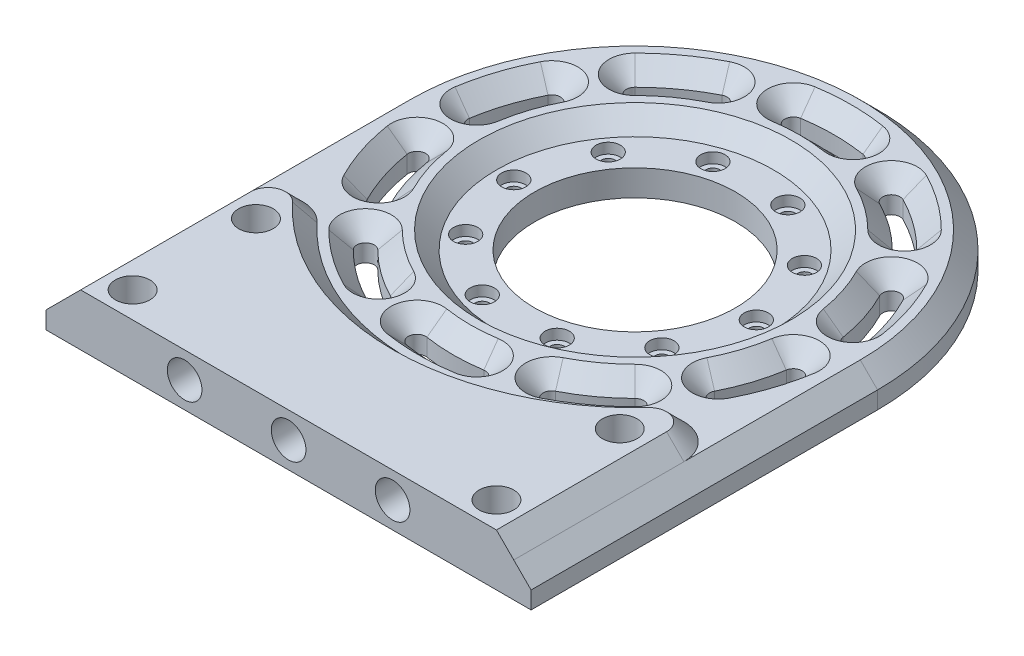
SolidWorks part; units mm, degrees
ref_plane "Front Plane" through (0, 0, 0) normal (0, 0, 1) x (1, 0, 0)
ref_plane "Top Plane" through (0, 0, 0) normal (0, 1, 0) x (1, 0, 0)
ref_plane "Right Plane" through (0, 0, 0) normal (1, 0, 0) x (0, 0, -1)
sketch "Sketch1" plane through (0, 0, 0) normal (0, 1, 0) x (1, 0, 0)
  line L0 (-70, 0) -> (-70, -100)
  line L1 (70, 0) -> (70, -100)
  line L2 (0, -100) -> (70, -100)
  line L3 (0, -100) -> (-70, -100)
  circle A2 centre (0, 0) radius 70
  circle A3 centre (0, 0) radius 29
  circle A4 centre (0, 0) radius 40
  circle A5 centre (-35, 0) radius 2
  circle A6 centre (-28.3156, 20.5725) radius 2
  circle A7 centre (-10.8156, 33.287) radius 2
  circle A8 centre (10.8156, 33.287) radius 2
  circle A9 centre (28.3156, 20.5725) radius 2
  circle A10 centre (35, 0) radius 2
  circle A11 centre (28.3156, -20.5725) radius 2
  circle A12 centre (10.8156, -33.287) radius 2
  circle A13 centre (-10.8156, -33.287) radius 2
  circle A14 centre (-28.3156, -20.5725) radius 2
  circle A15 centre (0, 0) radius 35
  point P36 (0, 0)
  dimension "D1" = 10
extrude "Boss-Extrude2" add sketch "Sketch1" along normal blind 10 contours A12 A15 A11 A10 A9 A8 A7 A6 A5 A14 A13 A3 | A4 A15 A12 A13 A14 A5 A6 A7 A8 A9 A10 A11 | A2 A4 | A2 L0 L3 L2 L1 region at (0, 0, 74.778) region at (0, 0, -68.0201) region at (-38.8686, 0, 0) region at (-32.8564, 0, -2.0832)
sketch "Sketch4" plane through (0, 10, 0) normal (0, 1, 0) x (1, 0, 0)
  circle A0 centre (0, 0) radius 29
  circle A1 centre (0, 0) radius 40
extrude "Cut-Extrude5" cut sketch "Sketch4" against normal blind 5
chamfer "Chamfer11" distance 5 angle 45 4 edges at (70, 10, 50) (0, 10, -70) (-70, 10, 50) (0, 10, 40)
sketch "Sketch7" plane through (0, 10, 0) normal (0, 1, 0) x (1, 0, 0)
  line L0 (0, 0) -> (-55, 0)
  line L1 (0, 0) -> (-28.3156, 20.5725)
  line L2 (-28.3156, 20.5725) -> (-44.4959, 32.3282)
  line L3 (0, 0) -> (-54.3229, 8.6039)
  line L4 (0, 0) -> (-52.3081, 16.9959)
  line L5 (0, 0) -> (-49.0054, 24.9695)
  circle A0 centre (0, 0) radius 55
  arc A1 (-49.0054, 24.9695) -> (-54.3229, 8.6039) centre (0, 0) ccw construction
  arc A2 (-51.2329, 26.1045) -> (-56.7921, 8.995) centre (0, 0) ccw
  arc A3 (-46.7778, 23.8345) -> (-51.8536, 8.2128) centre (0, 0) ccw
  arc A4 (-46.7778, 23.8345) -> (-51.2329, 26.1045) centre (-49.0054, 24.9695) ccw
  arc A5 (-56.7921, 8.995) -> (-51.8536, 8.2128) centre (-54.3229, 8.6039) ccw
  arc A6 (-24.9695, 49.0054) -> (-38.8909, 38.8909) centre (0, 0) ccw construction
  arc A7 (-26.1045, 51.2329) -> (-40.6586, 40.6586) centre (0, 0) ccw
  arc A8 (-23.8345, 46.7778) -> (-37.1231, 37.1231) centre (0, 0) ccw
  arc A9 (-23.8345, 46.7778) -> (-26.1045, 51.2329) centre (-24.9695, 49.0054) ccw
  arc A10 (-40.6586, 40.6586) -> (-37.1231, 37.1231) centre (-38.8909, 38.8909) ccw
  arc A11 (8.6039, 54.3229) -> (-8.6039, 54.3229) centre (0, 0) ccw construction
  arc A12 (8.995, 56.7921) -> (-8.995, 56.7921) centre (0, 0) ccw
  arc A13 (8.2128, 51.8536) -> (-8.2128, 51.8536) centre (0, 0) ccw
  arc A14 (8.2128, 51.8536) -> (8.995, 56.7921) centre (8.6039, 54.3229) ccw
  arc A15 (-8.995, 56.7921) -> (-8.2128, 51.8536) centre (-8.6039, 54.3229) ccw
  arc A16 (38.8909, 38.8909) -> (24.9695, 49.0054) centre (0, 0) ccw construction
  arc A17 (40.6586, 40.6586) -> (26.1045, 51.2329) centre (0, 0) ccw
  arc A18 (37.1231, 37.1231) -> (23.8345, 46.7778) centre (0, 0) ccw
  arc A19 (37.1231, 37.1231) -> (40.6586, 40.6586) centre (38.8909, 38.8909) ccw
  arc A20 (26.1045, 51.2329) -> (23.8345, 46.7778) centre (24.9695, 49.0054) ccw
  arc A21 (54.3229, 8.6039) -> (49.0054, 24.9695) centre (0, 0) ccw construction
  arc A22 (56.7921, 8.995) -> (51.2329, 26.1045) centre (0, 0) ccw
  arc A23 (51.8536, 8.2128) -> (46.7778, 23.8345) centre (0, 0) ccw
  arc A24 (51.8536, 8.2128) -> (56.7921, 8.995) centre (54.3229, 8.6039) ccw
  arc A25 (51.2329, 26.1045) -> (46.7778, 23.8345) centre (49.0054, 24.9695) ccw
  arc A26 (49.0054, -24.9695) -> (54.3229, -8.6039) centre (0, 0) ccw construction
  arc A27 (51.2329, -26.1045) -> (56.7921, -8.995) centre (0, 0) ccw
  arc A28 (46.7778, -23.8345) -> (51.8536, -8.2128) centre (0, 0) ccw
  arc A29 (46.7778, -23.8345) -> (51.2329, -26.1045) centre (49.0054, -24.9695) ccw
  arc A30 (56.7921, -8.995) -> (51.8536, -8.2128) centre (54.3229, -8.6039) ccw
  arc A31 (24.9695, -49.0054) -> (38.8909, -38.8909) centre (0, 0) ccw construction
  arc A32 (26.1045, -51.2329) -> (40.6586, -40.6586) centre (0, 0) ccw
  arc A33 (23.8345, -46.7778) -> (37.1231, -37.1231) centre (0, 0) ccw
  arc A34 (23.8345, -46.7778) -> (26.1045, -51.2329) centre (24.9695, -49.0054) ccw
  arc A35 (40.6586, -40.6586) -> (37.1231, -37.1231) centre (38.8909, -38.8909) ccw
  arc A36 (-8.6039, -54.3229) -> (8.6039, -54.3229) centre (0, 0) ccw construction
  arc A37 (-8.995, -56.7921) -> (8.995, -56.7921) centre (0, 0) ccw
  arc A38 (-8.2128, -51.8536) -> (8.2128, -51.8536) centre (0, 0) ccw
  arc A39 (-8.2128, -51.8536) -> (-8.995, -56.7921) centre (-8.6039, -54.3229) ccw
  arc A40 (8.995, -56.7921) -> (8.2128, -51.8536) centre (8.6039, -54.3229) ccw
  arc A41 (-38.8909, -38.8909) -> (-24.9695, -49.0054) centre (0, 0) ccw construction
  arc A42 (-40.6586, -40.6586) -> (-26.1045, -51.2329) centre (0, 0) ccw
  arc A43 (-37.1231, -37.1231) -> (-23.8345, -46.7778) centre (0, 0) ccw
  arc A44 (-37.1231, -37.1231) -> (-40.6586, -40.6586) centre (-38.8909, -38.8909) ccw
  arc A45 (-26.1045, -51.2329) -> (-23.8345, -46.7778) centre (-24.9695, -49.0054) ccw
  arc A46 (-54.3229, -8.6039) -> (-49.0054, -24.9695) centre (0, 0) ccw construction
  arc A47 (-56.7921, -8.995) -> (-51.2329, -26.1045) centre (0, 0) ccw
  arc A48 (-51.8536, -8.2128) -> (-46.7778, -23.8345) centre (0, 0) ccw
  arc A49 (-51.8536, -8.2128) -> (-56.7921, -8.995) centre (-54.3229, -8.6039) ccw
  arc A50 (-51.2329, -26.1045) -> (-46.7778, -23.8345) centre (-49.0054, -24.9695) ccw
  point P11 (-52.3081, 16.9959)
  point P20 (-32.3282, 44.4959)
  point P27 (0, 55)
  point P34 (32.3282, 44.4959)
  point P41 (52.3081, 16.9959)
  point P48 (52.3081, -16.9959)
  point P55 (32.3282, -44.4959)
  point P62 (0, -55)
  point P69 (-32.3282, -44.4959)
  point P76 (-52.3081, -16.9959)
  point P81 (0, 0)
  dimension "D1" = 9
  dimension "D4" = 10
  dimension "D2" = 9
  dimension "D3" = 9
extrude "Cut-Extrude8" cut sketch "Sketch7" against normal blind 10 contours A8 A10 A7 A9 | A13 A15 A12 A14 | A18 A20 A17 A19 | A22 A25 A23 A24 | A27 A30 A28 A29 | A32 A35 A33 A34 | A37 A40 A38 A39 | A42 A45 A43 A44 | A47 A50 A48 A49 | A2 A5 A3 A4
chamfer "Chamfer16" distance 5 angle 45 40 edges at (-54.6857, 10, 17.7685) (-54.7139, 10, 6.1347) (-47.8704, 10, 27.197) (-49.9305, 10, 16.2234) (-33.7977, 10, 46.5185) (-40.6586, 10, 37.1231) (-22.742, 10, 50.1403) (-30.8587, 10, 42.4734) (0, 10, 57.5) (-11.0731, 10, 53.9318) (11.0731, 10, 53.9318) (0, 10, 52.5) (33.7977, 10, 46.5185) (22.742, 10, 50.1403) (40.6586, 10, 37.1231) (30.8587, 10, 42.4734) (49.9305, 10, 16.2234) (47.8704, 10, 27.197) (54.7139, 10, 6.1347) (54.6857, 10, 17.7685) (49.9305, 10, -16.2234) (54.7139, 10, -6.1347) (47.8704, 10, -27.197) (54.6857, 10, -17.7685) (30.8587, 10, -42.4734) (40.6586, 10, -37.1231) (22.742, 10, -50.1403) (33.7977, 10, -46.5185) (0, 10, -52.5) (11.0731, 10, -53.9318) (-11.0731, 10, -53.9318) (0, 10, -57.5) (-30.8587, 10, -42.4734) (-22.742, 10, -50.1403) (-40.6586, 10, -37.1231) (-33.7977, 10, -46.5185) (-49.9305, 10, -16.2234) (-47.8704, 10, -27.197) (-54.7139, 10, -6.1347) (-54.6857, 10, -17.7685)
sketch "Sketch8" plane through (0, 10, 0) normal (0, 1, 0) x (1, 0, 0)
  line L2 (65, -100) -> (-65, -100) construction
  line L12 (-60, -50.8932) -> (-60, -100)
  line L13 (60, -100) -> (60, -50.8932)
  line L17 (-60, -100) -> (60, -100)
  arc A2 (-51.3333, -47.4939) -> (51.3333, -47.4939) centre (0, 0.0969) ccw
  arc A3 (60, -50.8932) -> (51.3333, -47.4939) centre (55, -50.8932) ccw
  arc A4 (-51.3333, -47.4939) -> (-60, -50.8932) centre (-55, -50.8932) ccw
  dimension "D1" = 5
extrude "Boss-Extrude3" add sketch "Sketch8" along normal blind 5
sketch "Sketch9" plane through (0, 15, 0) normal (0, 1, 0) x (1, 0, 0)
  line L9 (52.5, -56.9118) -> (52.5, -92.5)
  line L10 (52.5, -92.5) -> (-52.5, -92.5)
  line L11 (-52.5, -92.5) -> (-52.5, -56.9118)
  line L12 (52.5, -56.9118) -> (52.5, -92.5)
  line L13 (52.5, -92.5) -> (-52.5, -92.5)
  line L14 (-52.5, -92.5) -> (-52.5, -56.9118)
  circle A9 centre (-52.5, -56.9118) radius 5
  circle A10 centre (52.5, -56.9118) radius 5
  arc A11 (-52.5, -56.9118) -> (52.5, -56.9118) centre (0, 0.0969) ccw
  arc A12 (-52.5, -56.9118) -> (52.5, -56.9118) centre (0, 0.0969) ccw
  circle A13 centre (52.5, -92.5) radius 5
  circle A14 centre (-52.5, -92.5) radius 5
  dimension "D1" = 7.5
extrude "Cut-Extrude9" cut sketch "Sketch9" against normal blind 10 contours L14 A12 A9 | A12 L14 A9 | L14 A14 L13 | L13 A14 L14 | L13 A13 L12 | L12 A13 L13 | A12 A10 L12 | A10 A12 L12 region at (52.7089, 15, 56.4508) region at (51.1613, 15, 59.8666) region at (53.2074, 15, 93.2074) region at (50.3779, 15, 90.3779) region at (-52.7089, 15, 56.4508) region at (-51.1613, 15, 59.8666) region at (-53.2074, 15, 93.2074) region at (-50.3779, 15, 90.3779)
chamfer "Chamfer18" distance 5 angle 45 5 edges at (60, 10, 75.4466) (56.8257, 10, 46.2385) (0, 10, 69.9031) (-56.8257, 10, 46.2385) (-60, 10, 75.4466)
sketch "Sketch12" plane through (0, 5, 0) normal (0, 1, 0) x (1, 0, 0)
  circle A0 centre (-35, 0) radius 3.5
  circle A1 centre (-28.3156, 20.5725) radius 3.5
  circle A2 centre (-10.8156, 33.287) radius 3.5
  circle A3 centre (10.8156, 33.287) radius 3.5
  circle A4 centre (28.3156, 20.5725) radius 3.5
  circle A5 centre (35, 0) radius 3.5
  circle A6 centre (28.3156, -20.5725) radius 3.5
  circle A7 centre (10.8156, -33.287) radius 3.5
  circle A8 centre (-10.8156, -33.287) radius 3.5
  circle A9 centre (-28.3156, -20.5725) radius 3.5
  point P23 (0, 0)
  dimension "D1" = 10
extrude "Cut-Extrude12" cut sketch "Sketch12" against normal blind 3
sketch "Sketch13" plane through (0, 0, 0) normal (0, -1, 0) x (1, 0, 0)
  circle A0 centre (0, 0) radius 29
  circle A1 centre (0, 0) radius 40
  circle A2 centre (0, 0) radius 45
  circle A3 centre (-35, 0) radius 2
  circle A4 centre (-28.3156, 20.5725) radius 2
  circle A5 centre (-10.8156, 33.287) radius 2
  circle A6 centre (10.8156, 33.287) radius 2
  circle A7 centre (28.3156, 20.5725) radius 2
  circle A8 centre (35, 0) radius 2
  circle A9 centre (28.3156, -20.5725) radius 2
  circle A10 centre (10.8156, -33.287) radius 2
  circle A11 centre (-10.8156, -33.287) radius 2
  circle A12 centre (-28.3156, -20.5725) radius 2
  point P28 (0, 0)
  dimension "D1" = 10
extrude "Boss-Extrude4" add sketch "Sketch13" along normal blind 2.5 contours A1 A0 | A2 A1 region at (-38.8686, 0, 0) region at (-43.7272, 0, 0)
sketch "Sketch14" plane through (0, 0, 100) normal (0, 0, 1) x (1, 0, 0)
  line L0 (-60, 15) -> (-60, 0)
  line L1 (60.0315, 15) -> (60.0315, 0)
  line L2 (-60, 7.5) -> (-44.9961, 7.5)
  line L3 (-44.9961, 7.5) -> (-29.9921, 7.5)
  line L4 (-29.9921, 7.5) -> (0.0158, 7.5)
  line L5 (0.0158, 7.5) -> (30.0237, 7.5)
  line L6 (30.0237, 7.5) -> (45.0276, 7.5)
  line L7 (45.0276, 7.5) -> (60.0315, 7.5)
  line L8 (-60, 15) -> (60.0315, 15)
  line L9 (-60, 0) -> (60.0315, 0)
  circle A0 centre (0.0158, 7.5) radius 4
  circle A1 centre (-44.9961, 7.5) radius 4
  circle A2 centre (-29.9921, 7.5) radius 4
  circle A3 centre (30.0237, 7.5) radius 4
  circle A4 centre (45.0276, 7.5) radius 4
  circle A5 centre (-44.9961, 7.5) radius 5
  circle A6 centre (-29.9921, 7.5) radius 5
  circle A7 centre (0.0158, 7.5) radius 5
  circle A8 centre (30.0237, 7.5) radius 5
  circle A9 centre (45.0276, 7.5) radius 5
  point P5 (-29.9921, 7.5)
  point P9 (30.0237, 7.5)
  point P12 (-44.9961, 7.5)
  point P13 (45.0276, 7.5)
  dimension "D1" = 120.0315
  dimension "D2" = 15.0039
  dimension "D3" = 15
  dimension "D4" = 15.0039
  dimension "D5" = 15.0039
  dimension "D6" = 15.0039
  dimension "D7" = 30.0079
extrude "Cut-Extrude13" cut sketch "Sketch14" against normal blind 10 contours A6 | A7 | A8
